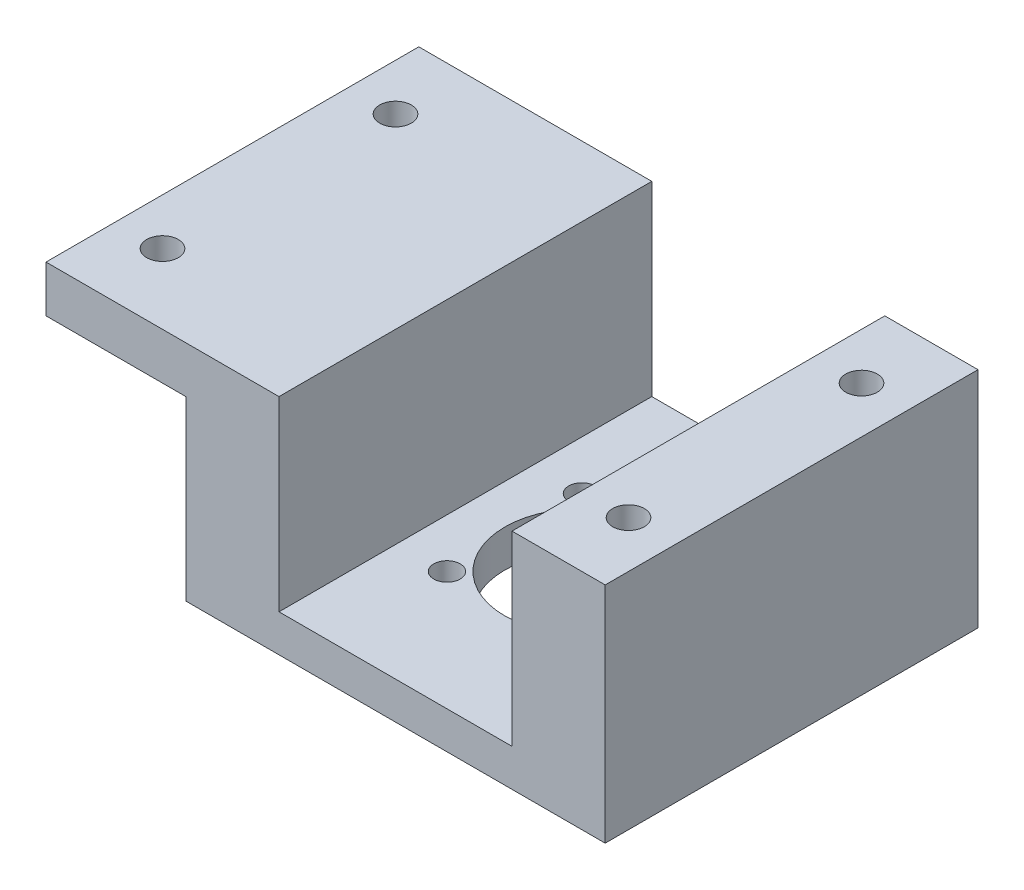
SolidWorks part; units mm, degrees
material "6061 Alloy"
ref_plane "Front Plane" through (0, 0, 0) normal (0, 0, 1) x (1, 0, 0)
ref_plane "Top Plane" through (0, 0, 0) normal (0, 1, 0) x (1, 0, 0)
ref_plane "Right Plane" through (0, 0, 0) normal (1, 0, 0) x (0, 0, -1)
sketch "Sketch1" plane through (0, 0, 0) normal (0, 1, 0) x (1, 0, 0)
  line L1 (-38.1, -25.4) -> (38.1, -25.4)
  line L2 (-38.1, -25.4) -> (-38.1, 25.4)
  line L3 (-38.1, 25.4) -> (38.1, 25.4)
  line L4 (38.1, -25.4) -> (38.1, 25.4)
  line L5 (-38.1, -25.4) -> (38.1, 25.4) construction
  line L6 (-38.1, 25.4) -> (38.1, -25.4) construction
  point P0 (0, 0)
  dimension "D1" = 76.2
  dimension "D2" = 50.8
extrude "Boss-Extrude1" add sketch "Sketch1" along normal blind 30.48
sketch "Sketch2" plane through (0, 0, 0) normal (0, -1, 0) x (1, 0, 0)
  line L0 (-38.1, 0) -> (38.1, 0) construction
  line L1 (-38.1, -25.4) -> (-38.1, 25.4) construction
  line L2 (38.1, 25.4) -> (38.1, -25.4) construction
  line L3 (0, 25.4) -> (0, -25.4) construction
  line L4 (-38.1, 25.4) -> (38.1, 25.4) construction
  line L5 (38.1, -25.4) -> (-38.1, -25.4) construction
  circle A1 centre (9.525, 0) radius 10.5
  point P12 (-9.525, 0)
  point P13 (9.525, 0)
  dimension "D3" = 21
  dimension "D1" = 19.05
  dimension "D2" = 9.525
extrude "Cut-Extrude1" cut sketch "Sketch2" against normal through all contours A1
sketch "Sketch3" plane through (0, 30.48, 0) normal (0, 1, 0) x (1, 0, 0)
  line L0 (9.525, 0) -> (-9.525, 0) construction
  line L1 (-12.7, -19.05) -> (12.7, -19.05)
  line L2 (-25.4, -6.35) -> (-25.4, 6.35)
  line L3 (-12.7, 19.05) -> (12.7, 19.05)
  line L4 (25.4, -6.35) -> (25.4, 6.35)
  line L5 (-25.4, -19.05) -> (25.4, 19.05) construction
  line L6 (-25.4, 19.05) -> (25.4, -19.05) construction
  arc A0 (12.7, 19.05) -> (25.4, 6.35) centre (12.7, 6.35) cw
  arc A1 (25.4, -6.35) -> (12.7, -19.05) centre (12.7, -6.35) cw
  arc A2 (-12.7, -19.05) -> (-25.4, -6.35) centre (-12.7, -6.35) cw
  arc A3 (-25.4, 6.35) -> (-12.7, 19.05) centre (-12.7, 6.35) cw
  point P0 (0, 0)
  dimension "D3" = 12.7
  dimension "D1" = 38.1
  dimension "D2" = 50.8
  dimension "D4" = 19.05
extrude "Cut-Extrude2" cut sketch "Sketch3" against normal blind 25.4
sketch "Sketch4" plane through (0, 0, 0) normal (0, -1, 0) x (1, 0, 0)
  line L0 (-31.75, 25.4) -> (-31.75, -25.4) construction
  line L1 (-38.1, 25.4) -> (38.1, 25.4) construction
  line L2 (38.1, -25.4) -> (-38.1, -25.4) construction
  line L3 (31.75, 25.4) -> (31.75, -25.4) construction
  line L4 (-38.1, -25.4) -> (-38.1, 25.4) construction
  line L5 (38.1, 25.4) -> (38.1, -25.4) construction
  line L6 (-31.75, 0) -> (31.75, 0) construction
  line L7 (0.3326, 9.1924) -> (18.7174, -9.1924) construction
  line L8 (18.7174, 9.1924) -> (0.3326, -9.1924) construction
  circle A1 centre (9.525, 0) radius 10.5 construction
  point P12 (-31.75, 15.875)
  point P13 (-31.75, -15.875)
  point P14 (31.75, 15.875)
  point P15 (31.75, -15.875)
  point P20 (9.525, 0)
  point P25 (9.525, 0)
  point P27 (0.3326, 9.1924)
  point P28 (18.7174, 9.1924)
  point P29 (18.7174, -9.1924)
  point P30 (0.3326, -9.1924)
  dimension "D1" = 6.35
  dimension "D2" = 6.35
  dimension "D3" = 31.75
  dimension "D4" = 45
  dimension "D5" = 45
  dimension "D6" = 26
hole_wizard "M3 Clearance Hole1" positions "3DSketch1" profile "Sketch5" hole size "M3" standard "ANSI Metric" end condition through all
sketch3d "3DSketch1"
  point P6 (0.3326, 0, 9.1924)
  point P9 (0.3326, 0, -9.1924)
  point P12 (18.7174, 0, 9.1924)
  point P15 (18.7174, 0, -9.1924)
sketch "Sketch5" plane through (0.3326, 0, 9.1924) normal (1, 0, 0) x (0, 0, -1)
  line L0 (0, 0) -> (0, 30.48)
  line L1 (0, 30.48) -> (1.8, 30.48)
  line L2 (1.8, 30.48) -> (1.8, 0)
  line L5 (1.8, 0) -> (0, 0)
  line L11 (0, -6.35) -> (0, 107.95) construction
  dimension "Thru Hole Dia." = 3.6
  dimension "Thru Hole Depth" = 30.48
hole_wizard "#6 Clearance Hole1" positions "3DSketch2" profile "Sketch6" hole size "#6" standard "ANSI Inch" end condition through all
sketch3d "3DSketch2"
  point P0 (-31.75, 0, 15.875)
  point P3 (-31.75, 0, -15.875)
  point P6 (31.75, 0, 15.875)
  point P9 (31.75, 0, -15.875)
sketch "Sketch6" plane through (-31.75, 0, 15.875) normal (1, 0, 0) x (0, 0, -1)
  line L0 (0, 0) -> (0, 30.48)
  line L1 (0, 30.48) -> (2.1526, 30.48)
  line L2 (2.1526, 30.48) -> (2.1526, 0)
  line L5 (2.1526, 0) -> (0, 0)
  line L11 (0, -6.35) -> (0, 107.95) construction
  dimension "Thru Hole Dia." = 4.3053
  dimension "Thru Hole Depth" = 30.48
sketch "Sketch7" plane through (0, 0, 25.4) normal (0, 0, 1) x (1, 0, 0)
  line L0 (20.025, 5.08) -> (-0.975, 5.08) construction
  line L1 (-38.1, 0) -> (-19.05, 0)
  line L2 (-38.1, 0) -> (-38.1, 24.13)
  line L3 (-38.1, 24.13) -> (-19.05, 24.13)
  line L4 (-19.05, 0) -> (-19.05, 24.13)
  line L5 (20.025, 5.08) -> (-0.975, 5.08)
  line L6 (9.525, 5.08) -> (9.525, 17.1843) construction
  line L7 (38.1, 30.48) -> (38.1, 0) construction
  line L8 (-38.1, 30.48) -> (38.1, 30.48) construction
  dimension "D1" = 6.35
extrude "Cut-Extrude3" cut sketch "Sketch7" against normal through all contours L2 L1 L4 L3
sketch "Sketch8" plane through (0, 5.08, 0) normal (0, 1, 0) x (1, 0, 0)
  line L0 (-38.1, -25.4) -> (38.1, -25.4) construction
  line L1 (-19.05, -25.4) -> (-6.35, -25.4)
  line L2 (-19.05, -25.4) -> (-19.05, 25.4)
  line L3 (-19.05, 25.4) -> (-6.35, 25.4)
  line L4 (-6.35, -25.4) -> (-6.35, 25.4)
  line L5 (38.1, 25.4) -> (-38.1, 25.4) construction
  line L6 (-19.05, 17.3485) -> (-19.05, -17.3485) construction
  line L7 (9.525, 0) -> (9.525, 15.6606) construction
  line L8 (25.4, -6.35) -> (25.4, 6.35) construction
extrude "Boss-Extrude2" add sketch "Sketch8" along normal up to surface (25.4 mm away) up to face at (-31.75, 30.48, 13.7224)
fillet "Fillet1" radius 12.7 2 edges at (-6.35, 17.78, 19.05) (-6.35, 17.78, -19.05)
sketch "Sketch9" plane through (0, 30.48, 0) normal (0, 1, 0) x (1, 0, 0)
  line L0 (-19.05, -17.3485) -> (-19.05, 17.3485) construction
  line L1 (-25.4, 6.35) -> (-25.4, -6.35) construction
  line L2 (-19.05, -17.3485) -> (-19.05, 17.3485)
  line L3 (-25.4, 6.35) -> (-25.4, -6.35)
  arc A0 (-25.4, -6.35) -> (-19.05, -17.3485) centre (-12.7, -6.35) ccw construction
  arc A1 (-19.05, 17.3485) -> (-25.4, 6.35) centre (-12.7, 6.35) ccw construction
  arc A2 (-25.4, -6.35) -> (-19.05, -17.3485) centre (-12.7, -6.35) ccw
  arc A3 (-19.05, 17.3485) -> (-25.4, 6.35) centre (-12.7, 6.35) ccw
extrude "Boss-Extrude3" add sketch "Sketch9" against normal up to surface (6.35 mm away) up to face at (-31.75, 24.13, -18.0276)
sketch "Sketch10" plane through (0, 0, 25.4) normal (0, 0, 1) x (1, 0, 0)
  line L0 (6.35, 30.48) -> (12.7, 30.48) construction
  line L1 (6.35, 5.08) -> (12.7, 5.08) construction
  line L2 (6.35, 30.48) -> (-6.35, 30.48) construction
  line L3 (25.4, 30.48) -> (12.7, 30.48) construction
  line L4 (25.4, 5.08) -> (25.4, 30.48) construction
  line L5 (25.4, 5.08) -> (12.7, 5.08) construction
  line L6 (6.35, 5.08) -> (-6.35, 5.08) construction
  line L7 (-6.35, 30.48) -> (-6.35, 5.08) construction
  line L8 (6.35, 30.48) -> (12.7, 30.48)
  line L9 (6.35, 5.08) -> (12.7, 5.08)
  line L10 (6.35, 30.48) -> (-6.35, 30.48)
  line L11 (25.4, 30.48) -> (12.7, 30.48)
  line L12 (25.4, 5.08) -> (25.4, 30.48)
  line L13 (25.4, 5.08) -> (12.7, 5.08)
  line L14 (6.35, 5.08) -> (-6.35, 5.08)
  line L15 (-6.35, 30.48) -> (-6.35, 5.08)
extrude "Cut-Extrude4" cut sketch "Sketch10" against normal through all
equation "\"D2@Sketch4\"=\"D1@Sketch4\""
equation "\"D2@Sketch2\"=\"D1@Sketch2\"/2"
